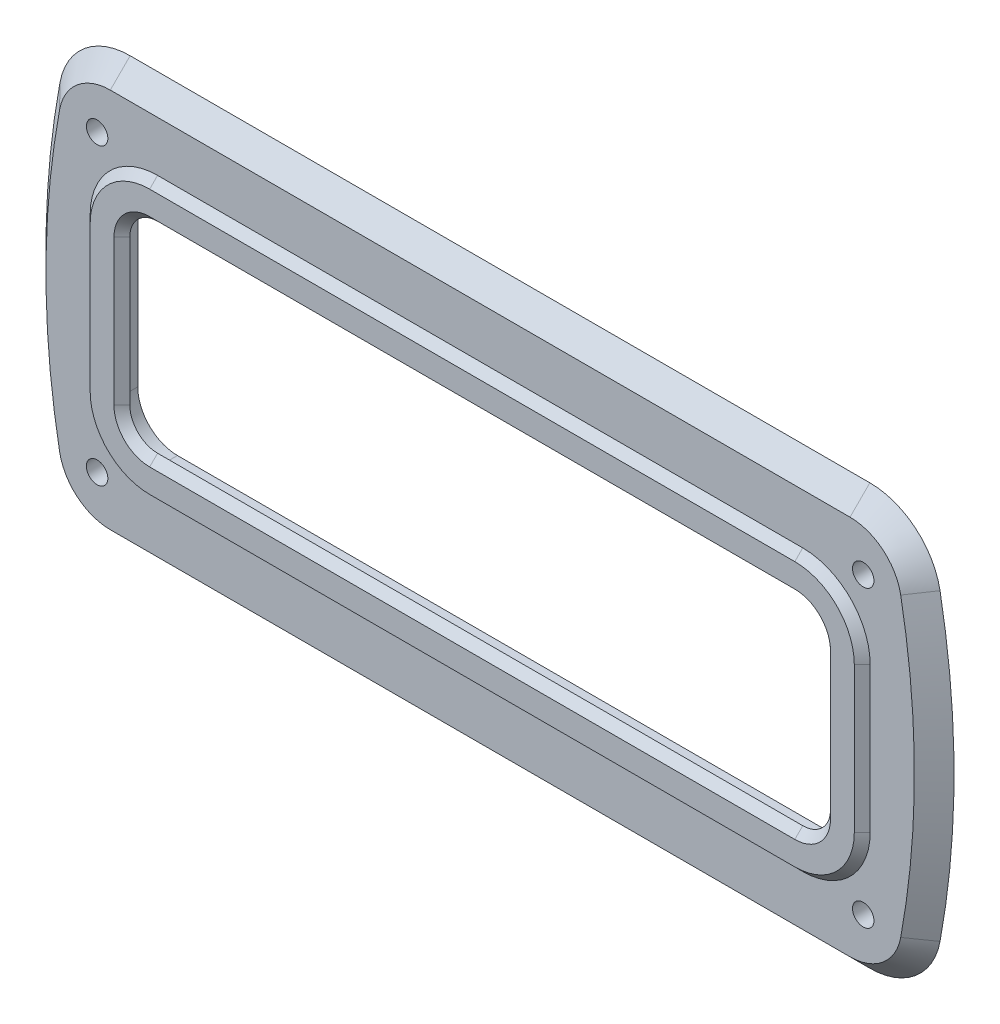
SolidWorks part; units mm, degrees
material "PLA"
ref_plane "Front Plane" through (0, 0, 0) normal (0, 0, 1) x (1, 0, 0)
ref_plane "Top Plane" through (0, 0, 0) normal (0, 1, 0) x (1, 0, 0)
ref_plane "Right Plane" through (0, 0, 0) normal (1, 0, 0) x (0, 0, -1)
sketch "Sketch1" plane through (0, 0, 0) normal (0, 0, 1) x (1, 0, 0)
  line L0 (-46.267, -27.3056) -> (46.983, -27.3056)
  line L1 (46.983, 25.6944) -> (-46.267, 25.6944)
  line L2 (-40.307, -14.9706) -> (41.023, -14.9706)
  line L3 (46.023, -9.9706) -> (46.023, 8.3594)
  line L4 (41.023, 13.3594) -> (-40.307, 13.3594)
  line L5 (-45.307, 8.3594) -> (-45.307, -9.9706)
  line L6 (-52.02, -25.2268) -> (-43.8425, -13.5061) construction
  line L7 (-43.8425, 11.895) -> (-52.02, 23.6156) construction
  line L8 (44.5586, 11.895) -> (52.736, 23.6156) construction
  line L9 (44.5586, -13.5061) -> (52.736, -25.2268) construction
  arc A0 (-55.1153, -19.9507) -> (-46.267, -27.3056) centre (-46.267, -18.3056) ccw
  arc A1 (46.983, -27.3056) -> (55.8314, -19.9507) centre (46.983, -18.3056) ccw
  arc A2 (55.8314, -19.9507) -> (55.8314, 18.3395) centre (-47.142, -0.8056) ccw
  arc A3 (55.8314, 18.3395) -> (46.983, 25.6944) centre (46.983, 16.6944) ccw
  arc A4 (-46.267, 25.6944) -> (-55.1153, 18.3395) centre (-46.267, 16.6944) ccw
  arc A5 (-55.1153, 18.3395) -> (-55.1153, -19.9507) centre (47.858, -0.8056) ccw
  circle A6 centre (48.6473, -19.3664) radius 1.35
  circle A7 centre (48.6473, 17.7553) radius 1.35
  circle A8 centre (-47.9312, 17.7553) radius 1.35
  arc A10 (-45.307, -9.9706) -> (-40.307, -14.9706) centre (-40.307, -9.9706) ccw
  arc A11 (41.023, -14.9706) -> (46.023, -9.9706) centre (41.023, -9.9706) ccw
  arc A12 (46.023, 8.3594) -> (41.023, 13.3594) centre (41.023, 8.3594) ccw
  arc A13 (-40.307, 13.3594) -> (-45.307, 8.3594) centre (-40.307, 8.3594) ccw
  circle A14 centre (-47.9312, -19.3664) radius 1.3539
  point P43 (48.6473, -19.3664)
  point P45 (-47.9312, 17.7553)
  point P46 (48.6473, 17.7553)
extrude "Boss-Extrude1" add sketch "Sketch1" along normal blind 2.5
sketch "Sketch2" plane through (0, 0, 2.5) normal (0, 0, 1) x (1, 0, 0)
  line L24 (49.523, -9.9706) -> (49.523, 8.3594)
  line L25 (-40.307, -18.4706) -> (41.023, -18.4706)
  line L26 (-48.807, 8.3594) -> (-48.807, -9.9706)
  line L27 (41.023, 16.8594) -> (-40.307, 16.8594)
  line L28 (49.523, -9.9706) -> (49.523, 8.3594)
  line L29 (-40.307, -18.4706) -> (41.023, -18.4706)
  line L30 (-48.807, 8.3594) -> (-48.807, -9.9706)
  line L31 (41.023, 16.8594) -> (-40.307, 16.8594)
  line L34 (41.023, 11.8594) -> (-40.307, 11.8594)
  line L35 (-43.807, 8.3594) -> (-43.807, -9.9706)
  line L36 (-40.307, -13.4706) -> (41.023, -13.4706)
  line L37 (44.523, -9.9706) -> (44.523, 8.3594)
  arc A20 (49.523, 8.3594) -> (41.023, 16.8594) centre (41.023, 8.3594) ccw
  arc A21 (41.023, -18.4706) -> (49.523, -9.9706) centre (41.023, -9.9706) ccw
  arc A22 (-48.807, -9.9706) -> (-40.307, -18.4706) centre (-40.307, -9.9706) ccw
  arc A23 (-40.307, 16.8594) -> (-48.807, 8.3594) centre (-40.307, 8.3594) ccw
  arc A24 (49.523, 8.3594) -> (41.023, 16.8594) centre (41.023, 8.3594) ccw
  arc A25 (41.023, -18.4706) -> (49.523, -9.9706) centre (41.023, -9.9706) ccw
  arc A26 (-48.807, -9.9706) -> (-40.307, -18.4706) centre (-40.307, -9.9706) ccw
  arc A27 (-40.307, 16.8594) -> (-48.807, 8.3594) centre (-40.307, 8.3594) ccw
  arc A33 (44.523, 8.3594) -> (41.023, 11.8594) centre (41.023, 8.3594) ccw
  arc A34 (-40.307, 11.8594) -> (-43.807, 8.3594) centre (-40.307, 8.3594) ccw
  arc A35 (-43.807, -9.9706) -> (-40.307, -13.4706) centre (-40.307, -9.9706) ccw
  arc A36 (41.023, -13.4706) -> (44.523, -9.9706) centre (41.023, -9.9706) ccw
  dimension "D1" = 3.5
  dimension "D2" = 5
extrude "Boss-Extrude2" add sketch "Sketch2" along normal blind 1
chamfer "Chamfer1" distance 1 angle 45 16 edges at (-42.7818, 10.8343, 3.5) (-43.807, -0.8056, 3.5) (-42.7818, -12.4454, 3.5) (0.358, -13.4706, 3.5) (43.4979, -12.4454, 3.5) (44.523, -0.8056, 3.5) (43.4979, 10.8343, 3.5) (0.358, 11.8594, 3.5) (49.523, -0.8056, 3.5) (47.0334, -15.981, 3.5) (0.358, -18.4706, 3.5) (-46.3174, -15.981, 3.5) (-48.807, -0.8056, 3.5) (-46.3174, 14.3698, 3.5) (0.358, 16.8594, 3.5) (47.0334, 14.3698, 3.5)
chamfer "Chamfer2" distance 2.5 angle 45 8 edges at (0.358, -27.3056, 2.5) (52.736, -25.2268, 2.5) (-52.02, -25.2268, 2.5) (57.596, -0.8056, 2.5) (-56.88, -0.8056, 2.5) (52.736, 23.6156, 2.5) (-52.02, 23.6156, 2.5) (0.358, 25.6944, 2.5)
